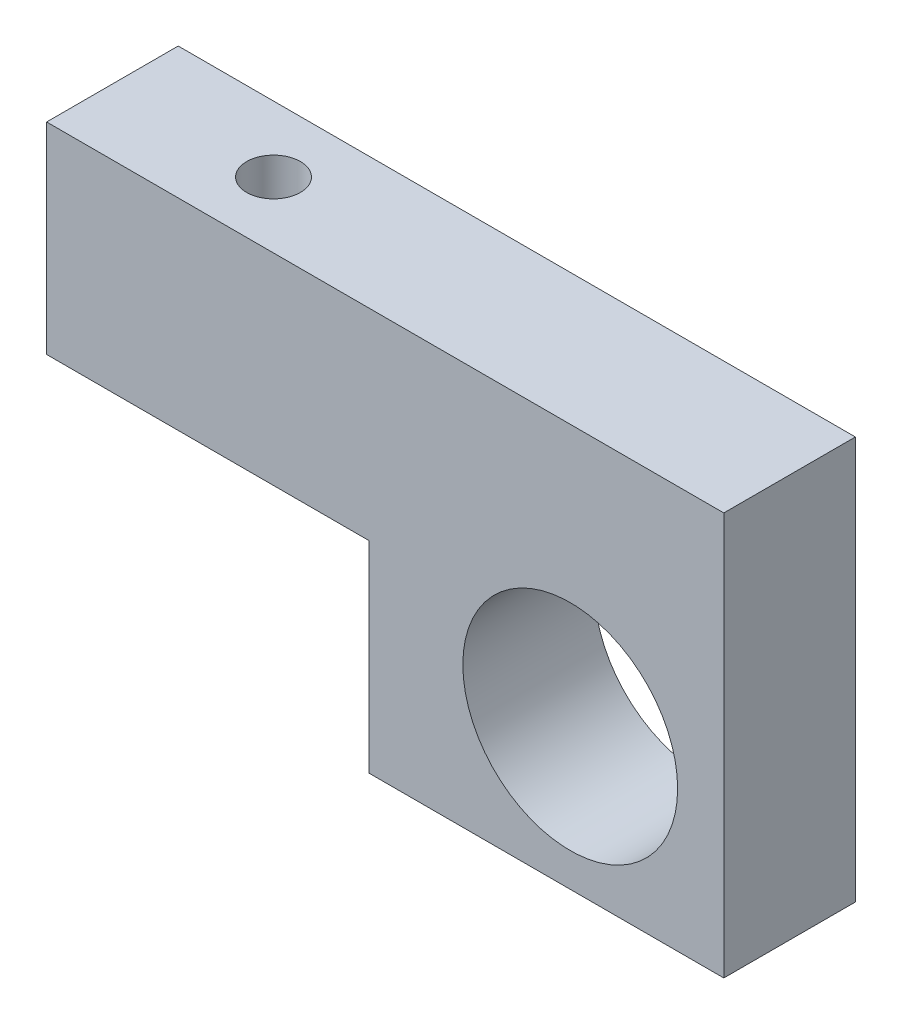
SolidWorks part; units mm, degrees
material "ABS"
ref_plane "Front Plane" through (0, 0, 0) normal (0, 0, 1) x (1, 0, 0)
ref_plane "Top Plane" through (0, 0, 0) normal (0, 1, 0) x (1, 0, 0)
ref_plane "Right Plane" through (0, 0, 0) normal (1, 0, 0) x (0, 0, -1)
sketch "Sketch1" plane through (0, 0, 0) normal (0, 0, 1) x (1, 0, 0)
  line L0 (-24, 15) -> (0, 15)
  line L1 (0, 15) -> (0, 0)
  line L2 (0, 0) -> (93, 0)
  line L3 (93, 0) -> (93, 102.7)
  line L4 (93, 102.7) -> (0, 102.7)
  line L5 (0, 102.7) -> (0, 30)
  line L6 (0, 30) -> (-24, 30)
  line L7 (-24, 30) -> (-24, 15)
  circle A0 centre (15, 10.5) radius 8
  circle A1 centre (70, 72) radius 11
  circle A2 centre (15, 10.5) radius 11
  dimension "D1" = 15
  dimension "D10" = 16
  dimension "D11" = 22
  dimension "D12" = 22
  dimension "D2" = 24
  dimension "D3" = 72.7
  dimension "D4" = 15
  dimension "D5" = 15
  dimension "D6" = 10.5
  dimension "D7" = 82.5061
  dimension "D8" = 72
  dimension "D9" = 93
extrude "Boss-Extrude1" add sketch "Sketch1" along normal blind 4.8 contours A2 L2 L3 L4 L5 L6 L7 L0 L1 A1 | L2 A2 A0 region at (44.5238, 51.0418, 0) region at (8.6656, 19.1141, 0)
sketch "Sketch2" plane through (0, 0, 4.8) normal (0, 0, 1) x (1, 0, 0)
  line L0 (93, 0) -> (93, 102.7) construction
  line L1 (48.1786, 92.7632) -> (93, 92.7632)
  line L2 (48.1786, 92.7632) -> (48.1786, 52.666)
  line L3 (48.1786, 52.666) -> (93, 52.666)
  line L4 (93, 92.7632) -> (93, 52.666)
  line L5 (48.1786, 92.7632) -> (93, 52.666) construction
  line L6 (48.1786, 52.666) -> (93, 92.7632) construction
  circle A0 centre (70, 72) radius 11
  circle A1 centre (70, 72) radius 4.15
  point P8 (70.5893, 72.7146)
  line M4 (93, 0) -> (93, 102.7)
  circle M10 centre (70, 72) radius 11
  dimension "D1" = 22
  dimension "D2" = 8.3
extrude "Boss-Extrude2" add sketch "Sketch2" along normal blind 8.2 contours L2 L3 L1 M4 M10 region at (70.5893, 92.1618, 4.8)
sketch "Sketch3" plane through (0, 0, 4.8) normal (0, 0, 1) x (1, 0, 0)
  line L1 (-24, 15) -> (0, 15)
  line L2 (-24, 15) -> (-24, 30)
  line L3 (-24, 30) -> (0, 30)
  line L4 (0, 15) -> (0, 30)
  line L5 (-24, 15) -> (0, 30) construction
  line L6 (-24, 30) -> (0, 15) construction
  line L7 (0, 0) -> (93, 0)
  line L8 (0, 0) -> (0, 52.666)
  line L9 (0, 52.666) -> (93, 52.666)
  line L10 (93, 0) -> (93, 52.666)
  line L11 (0, 0) -> (93, 52.666) construction
  line L12 (0, 52.666) -> (93, 0) construction
  circle A0 centre (15, 10.5) radius 8
  point P4 (-12, 22.5)
  point P11 (46.5, 26.333)
  circle M1 centre (15, 10.5) radius 8
  line M6 (0, 102.7) -> (0, 30)
  line M7 (0, 30) -> (-24, 30)
  line M8 (-24, 30) -> (-24, 15)
  line M9 (-24, 15) -> (0, 15)
  line M10 (0, 15) -> (0, 0)
  line M11 (0, 0) -> (93, 0)
  line M12 (93, 0) -> (93, 52.666)
  line M13 (93, 52.666) -> (48.1786, 52.666)
extrude "Boss-Extrude3" add sketch "Sketch3" along normal blind 5 contours L4 M9 M7 M8 | L9 L4 M6 M10 M11 M12 M13 M1 region at (-12, 22.5, 4.8) region at (47.8484, 27.0108, 4.8)
sketch "Sketch4" plane through (0, 83.2317, 0) normal (0, -1, 0) x (1, 0, 0)
  line L0 (0, 9.8) -> (0, 4.8) construction
  line L1 (0, 4.8) -> (48.1786, 4.8)
  line L2 (0, 4.8) -> (0, 45.3)
  line L3 (0, 45.3) -> (48.1786, 45.3)
  line L4 (48.1786, 4.8) -> (48.1786, 45.3)
  line L5 (0, 4.8) -> (48.1786, 45.3) construction
  line L6 (0, 45.3) -> (48.1786, 4.8) construction
  line L7 (0, 4.8) -> (48.1786, 4.8) construction
  line L8 (48.1786, 13) -> (48.1786, 9.8) construction
  line L9 (0, 0) -> (93, 0) construction
  line L10 (0, 45.3) -> (-5, 45.3)
  line L11 (0, 45.3) -> (0, 0)
  line L12 (0, 0) -> (-5, 0)
  line L13 (-5, 45.3) -> (-5, 0)
  line L14 (0, 45.3) -> (-5, 0) construction
  line L15 (0, 0) -> (-5, 45.3) construction
  circle A0 centre (13.9465, 30.3) radius 6.35
  circle A1 centre (13.9465, 23.3) radius 18.5
  circle A3 centre (29.4465, 23.3) radius 2
  circle A4 centre (21.6965, 9.8766) radius 2
  circle A5 centre (6.1965, 9.8766) radius 2
  point P10 (24.0893, 25.05)
  point P30 (-2.5, 22.65)
  arc M5 (5.039, 30.9329) -> (22.854, 30.9329) centre (13.9465, 30.3) ccw
  arc M7 (23.1854, 31.0672) -> (4.7077, 31.0672) centre (13.9465, 23.3) cw
  circle M9 centre (21.6965, 9.8766) radius 1.6
  circle M10 centre (6.1965, 9.8766) radius 1.6
  circle M11 centre (-1.5535, 23.3) radius 1.6
  circle M12 centre (6.1965, 36.7234) radius 1.6
  circle M13 centre (21.6965, 36.7234) radius 1.6
  circle M15 centre (27.3699, 31.05) radius 2.1
  circle M16 centre (0.5231, 31.05) radius 2.1
  circle M17 centre (13.9465, 7.8) radius 2.1
  circle M19 centre (13.9465, 23.3) radius 18.5
  dimension "D1" = 12.7
  dimension "D2" = 15
  dimension "D3" = 4
  dimension "D4" = 4
  dimension "D5" = 4
  dimension "D6" = 5
  dimension "D7" = 0
extrude "Boss-Extrude4" add sketch "Sketch4" along normal blind 5 contours L1 L4 L3 M19 | A0 L3 L2 A5 A4 A3 M12 M19 M16 M11 M13 M17 M15 M5 M7 | M5 M7 | M17 | A4 M9 | M9 | M10 | A5 M10 | M15 | L2 M16 | L2 L1 M19 region at (3.3557, 83.2317, 6.6306) region at (34.3643, 83.2317, 27.4815) region at (15.1399, 83.2317, 22.3686) region at (1.1393, 83.2317, 31.05) region at (19.7531, 83.2317, 9.8766) region at (4.2531, 83.2317, 9.8766) region at (21.6965, 83.2317, 9.8766) region at (6.1965, 83.2317, 9.8766) region at (27.3699, 83.2317, 31.05) region at (13.9465, 83.2317, 7.8)
sketch "Sketch5" plane through (48.1786, 0, 0) normal (1, 0, 0) x (0, 0, -1)
  line L0 (-45.3, 83.2317) -> (-13, 92.7632)
  line L1 (-13, 92.7632) -> (-4.8, 92.7632)
  line L2 (-4.8, 92.7632) -> (-4.8, 78.2317)
  line L3 (-4.8, 78.2317) -> (-45.3, 78.2317)
  line L4 (-45.3, 78.2317) -> (-45.3, 83.2317)
extrude "Boss-Extrude5" add sketch "Sketch5" against normal blind 5
sketch "Sketch6" plane through (0, 0, 4.8) normal (0, 0, 1) x (1, 0, 0)
  line L0 (0, 78.2317) -> (0, 52.666) construction
  line L1 (0, 78.2317) -> (48.1786, 78.2317)
  line L2 (0, 78.2317) -> (0, 52.666)
  line L3 (0, 52.666) -> (48.1786, 52.666)
  line L4 (48.1786, 78.2317) -> (48.1786, 52.666)
  line L5 (0, 78.2317) -> (48.1786, 52.666) construction
  line L6 (0, 52.666) -> (48.1786, 78.2317) construction
  line L7 (0, 78.2317) -> (48.1786, 78.2317) construction
  point P4 (24.0893, 65.4489)
extrude "Boss-Extrude6" add sketch "Sketch6" along normal up to surface (5 mm away) up to face at (20.6865, 27.5553, 9.8)
ref_plane "Plane1" through (3.9877, 7.5909, 34.4544) normal (0.9262, 0.2454, -0.2862) x (0.0581, -0.8429, -0.5349)
sketch "Sketch8" plane through (0, 30, 0) normal (0, 1, 0) x (1, 0, 0)
  line L0 (0, 0) -> (-24, -9.8)
  line L1 (-24, -9.8) -> (-24, 0)
  line L2 (-24, 0) -> (0, -9.8)
  circle A0 centre (-12, -4.9) radius 2
  dimension "D1" = 4
extrude "Cut-Extrude1" cut sketch "Sketch8" against normal through all contours A0
sketch "Sketch9" plane through (0, 0, 0) normal (0, 0, -1) x (-1, 0, 0)
  line L1 (0, 30) -> (-93, 30)
  line L2 (0, 30) -> (0, 102.7)
  line L3 (0, 102.7) -> (-93, 102.7)
  line L4 (-93, 30) -> (-93, 102.7)
extrude "Cut-Extrude2" cut sketch "Sketch9" against normal blind 100
sketch "Sketch10" plane through (0, 0, 9.8) normal (0, 0, 1) x (1, 0, 0)
  line L0 (93, 30) -> (-24, 30) construction
  line L1 (93, 0) -> (26.438, 0)
  line L2 (93, 0) -> (93, 30)
  line L3 (93, 30) -> (26.438, 30)
  line L4 (26.438, 0) -> (26.438, 30)
extrude "Cut-Extrude3" cut sketch "Sketch10" against normal blind 100
